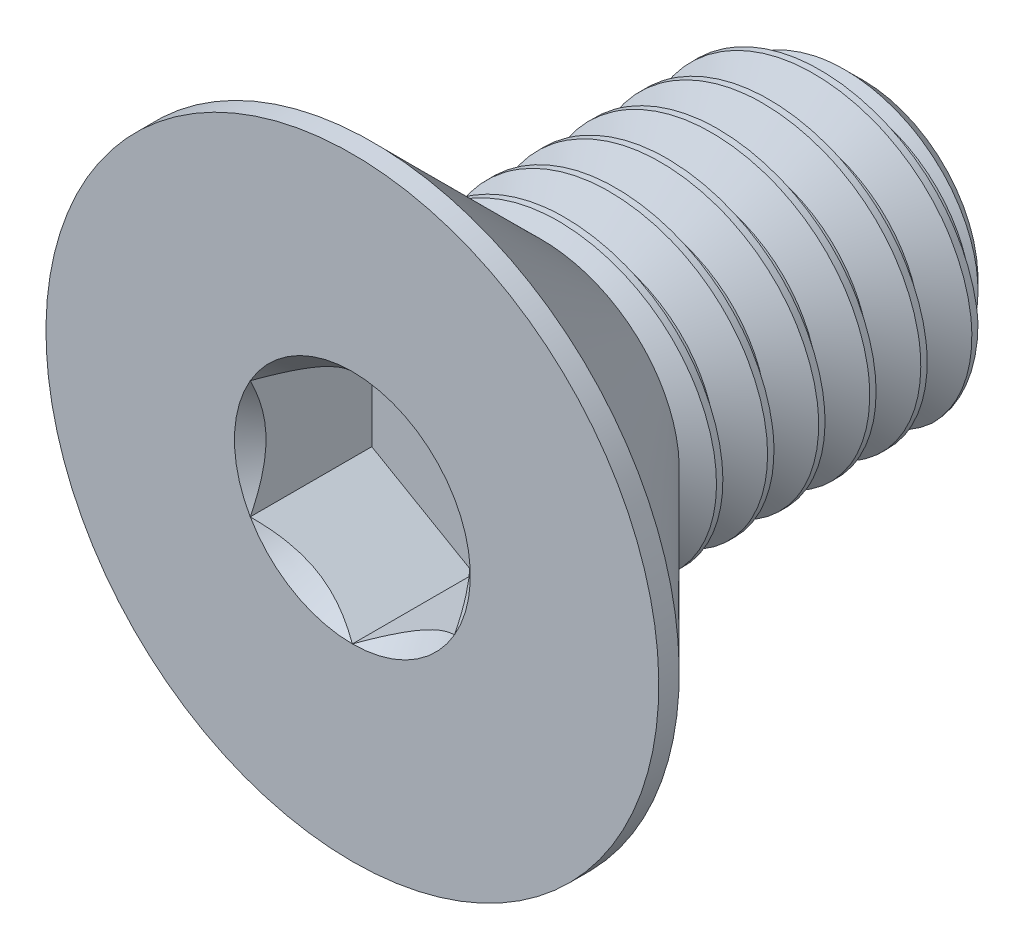
SolidWorks part; units mm, degrees
ref_plane "Front" through (0, 0, 0) normal (0, 0, 1) x (1, 0, 0)
ref_plane "Top" through (0, 0, 0) normal (0, 1, 0) x (1, 0, 0)
ref_plane "Right" through (0, 0, 0) normal (1, 0, 0) x (0, 0, -1)
sketch "Sketch1" plane through (0, 0, 0) normal (1, 0, 0) x (0, 0, -1)
  line L0 (0, 3) -> (0.2, 3) construction
  line L1 (0.2, 3) -> (1.7, 1.5) construction
  line L2 (0, 1.5) -> (5, 1.5)
  line L3 (5, 1.5) -> (5, 0)
  line L4 (5, 0) -> (0, 0)
  line L5 (0, 0) -> (0, 3) construction
  line L6 (0, 3) -> (0, -3) construction
  line L7 (5, 1.5) -> (5, -1.5) construction
  line L8 (0, -3) -> (0.2, -3) construction
  line L9 (0.2, -3) -> (1.7, -1.5) construction
  line L11 (0, 1.5) -> (0, 0)
  line L12 (1.7, 1.5) -> (1.7, 0) construction
  dimension "Head Ht" = 1.7
  dimension "Head Dia" = 6
  dimension "Dia" = 3
  dimension "Lg" = 5
  dimension "Head Angle" = 90
revolve "Revolve1" add sketch "Sketch1" angle 360 mid plane about L4
sketch "Sketch3" plane through (0, 0, -5) normal (0, 0, -1) x (-1, 0, 0)
  circle A0 centre (0, 0) radius 1.5
curve "Helix/Spiral1" pitch 0.5 height 5 radius 1.5 centre (0, 0, -5) axis (0, 0, 1) start towards (0, 1, 0)
sketch "Sketch2" plane through (0, 0, 0) normal (1, 0, 0) x (0, 0, -1)
  line L0 (5, 1.5) -> (5.4375, 1.5)
  line L1 (5.4375, 1.5) -> (5.25, 1.1752)
  line L2 (5.25, 1.1752) -> (5.1875, 1.1752)
  line L3 (5.1875, 1.1752) -> (5, 1.5)
  line L4 (5.0938, 1.3376) -> (5.3437, 1.3376) construction
  dimension "D1" = 60
  dimension "D2" = 0.0625
  dimension "D3" = 0.25
chamfer "Chamfer1" distance 0.375 angle 45 1 edges at (0, 1.5, -5)
sweep "Cut-Sweep1" cut profiles "Sketch2" path "Helix/Spiral1" align with end faces yes
sketch "Sketch7" plane through (0, 0, 0) normal (1, 0, 0) x (0, 0, -1)
  line L0 (0, 3) -> (0.2, 3) construction
  line L1 (0.2, 3) -> (1.7, 1.5) construction
  line L2 (0, 3) -> (0.2, 3)
  line L3 (0.2, 3) -> (1.7, 1.5)
  line L4 (1.7, 1.5) -> (1.7, 0) construction
  line L5 (1.7, 1.5) -> (1.7, 0)
  line L7 (0, 0) -> (0, 3) construction
  line L8 (0, 0) -> (0, 3)
  line L9 (0, 0) -> (1.7, 0)
  line L10 (3.3, 0) -> (-3.3, 0) construction
revolve "Revolve2" add sketch "Sketch7" angle 360 mid plane about L9
ref_plane "Plane1" through (0, 0, -1.7) normal (0, 0, 1) x (1, 0, 0)
sketch "Sketch8" plane through (0, 0, -1.7) normal (0, 0, 1) x (1, 0, 0)
  circle A0 centre (0, 0) radius 1.5
extrude "Boss-Extrude1" add sketch "Sketch8" against normal through all draft 45
sketch "Sketch5" plane through (0, 0, 0) normal (0, 0, 1) x (1, 0, 0)
  line L1 (1, -0.5774) -> (1, 0.5774)
  line L2 (1, 0.5774) -> (0, 1.1547)
  line L3 (0, 1.1547) -> (-1, 0.5774)
  line L4 (-1, 0.5774) -> (-1, -0.5774)
  line L5 (-1, -0.5774) -> (0, -1.1547)
  line L6 (0, -1.1547) -> (1, -0.5774)
  circle A0 centre (0, 0) radius 1 construction
  dimension "Hex" = 2
extrude "Cut-Extrude2" cut sketch "Sketch5" against normal blind 1.19
sketch "Sketch6" plane through (0, 0, 0) normal (0, 0, 1) x (1, 0, 0)
  circle A0 centre (0, 0) radius 1.1547
extrude "Cut-Extrude3" cut sketch "Sketch6" against normal blind 1.19 draft 45
sketch "Sketch9" [suppressed] plane through (0, 0, -5.5) normal (0, 0, 1) x (1, 0, 0)
  circle A1 centre (0, 0) radius 5
  circle A2 centre (0, 0) radius 5
  point P0 (0, 5)
  dimension "D1" = 0
extrude "Boss-Extrude2" [suppressed] add sketch "Sketch9" against normal offset from surface (18.5 mm away) 26 up to face at (0, 1.125, -5)
fillet "Fillet1" [suppressed] radius 0.3
sketch "Sketch10" plane through (0, 0, 0) normal (1, 0, 0) x (0, 0, -1)
  line L0 (5, 1.5) -> (5, -1.5) construction
  point P0 (4.25, -1.5)
  dimension "D1" = 0.75
equation "\"D3@Helix/Spiral1\" = \"Lg@Sketch1\""
equation "\"D2@Sketch2\" = \"D4@Helix/Spiral1\" * .125"
equation "\"D3@Sketch2\" = \"D4@Helix/Spiral1\" * .5"
equation "\"D1@Chamfer1\" = \"D4@Helix/Spiral1\" * .75"
equation "\"D1@Cut-Extrude2\" = \"Head Ht@Sketch1\" * .7"
equation "\"D1@Sketch10\" = \"D4@Helix/Spiral1\" * 1.5"
equation "\"D1@Cut-Extrude3\" = \"D1@Cut-Extrude2\""
equation "\"D1@Fillet1\" = \"Dia@Sketch1\" * .1"
